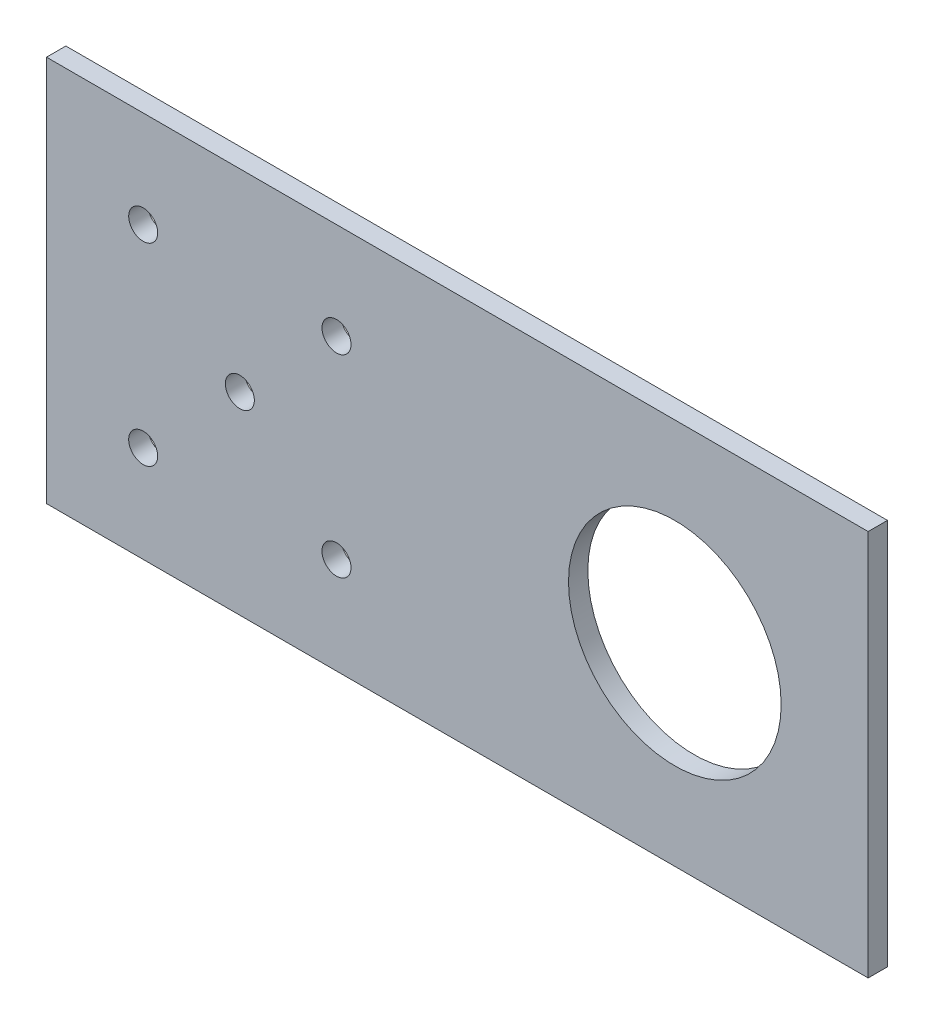
SolidWorks part; units mm, degrees
ref_plane "Front Plane" through (0, 0, 0) normal (0, 0, 1) x (1, 0, 0)
ref_plane "Top Plane" through (0, 0, 0) normal (0, 1, 0) x (1, 0, 0)
ref_plane "Right Plane" through (0, 0, 0) normal (1, 0, 0) x (0, 0, -1)
sketch "Sketch1" plane through (0, 0, 0) normal (0, 0, 1) x (1, 0, 0)
  line L1 (-42.5, 20) -> (42.5, 20)
  line L2 (-42.5, 20) -> (-42.5, -20)
  line L3 (-42.5, -20) -> (42.5, -20)
  line L4 (42.5, 20) -> (42.5, -20)
  line L5 (-42.5, 20) -> (42.5, -20) construction
  line L6 (-42.5, -20) -> (42.5, 20) construction
  point P0 (0, 0)
  dimension "D1" = 85
  dimension "D2" = 40
extrude "Boss-Extrude1" add sketch "Sketch1" along normal mid plane 2
sketch "Sketch2" plane through (0, 0, 1) normal (0, 0, 1) x (1, 0, 0)
  line L0 (1.1, 0) -> (-1.1, 0) construction
  line L1 (42.5, -20) -> (42.5, 20) construction
  line L2 (-32.5, 10) -> (-12.5, 10) construction
  line L3 (42.5, 20) -> (-42.5, 20) construction
  line L4 (-42.5, 20) -> (-42.5, -20) construction
  line L5 (-42.5, -20) -> (42.5, -20) construction
  circle A0 centre (22.5, 0) radius 11
  circle A1 centre (-22.5, 0) radius 1.5
  circle A2 centre (-32.5, 10) radius 1.5
  circle A3 centre (-12.5, 10) radius 1.5
  circle A4 centre (-12.5, -10) radius 1.5
  circle A5 centre (-32.5, -10) radius 1.5
  point P22 (0, 0)
  point P23 (0, 0)
  dimension "D1" = 22
  dimension "D3" = 3
  dimension "D2" = 20
  dimension "D6" = 20
  dimension "D7" = 10
  dimension "D8" = 10
  dimension "D9" = 20
  dimension "D10" = 10
  dimension "D4" = 2
  dimension "D5" = 2
extrude "Cut-Extrude1" cut sketch "Sketch2" against normal blind 2
